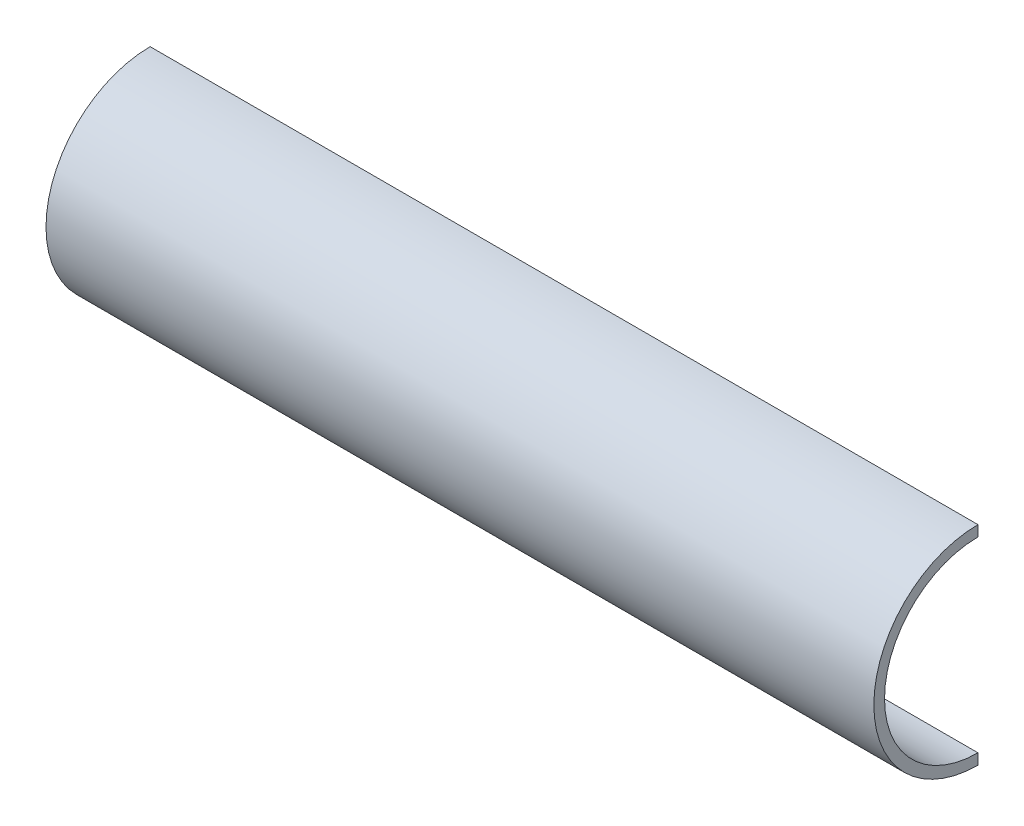
SolidWorks part; units mm, degrees
material "7050-T73510"
ref_plane "Front Plane" through (0, 0, 0) normal (0, 0, 1) x (1, 0, 0)
ref_plane "Top Plane" through (0, 0, 0) normal (0, 1, 0) x (1, 0, 0)
ref_plane "Right Plane" through (0, 0, 0) normal (1, 0, 0) x (0, 0, -1)
sketch "Sketch1" plane through (0, 0, 0) normal (1, 0, 0) x (0, 0, -1)
  line L0 (0, 35) -> (7, 35)
  line L1 (7, 35) -> (7, -35)
  line L2 (7, -35) -> (0, -35)
  line L3 (0, 39) -> (7, 39)
  line L4 (7, 39) -> (7, 35)
  line L5 (0, -39) -> (7, -39)
  line L6 (7, -39) -> (7, -35)
  line L7 (0, -39) -> (0, 39)
  line L9 (-35, 0) -> (7, 0) construction
  circle A0 centre (0, 0) radius 35
  circle A1 centre (0, 0) radius 39
  dimension "D1" = 70
  dimension "D3" = 4
  dimension "D2" = 7
extrude "Boss-Extrude1" add sketch "Sketch1" along normal blind 310 contours L7 A1 A0 region at (0, 0, 35.8721)
